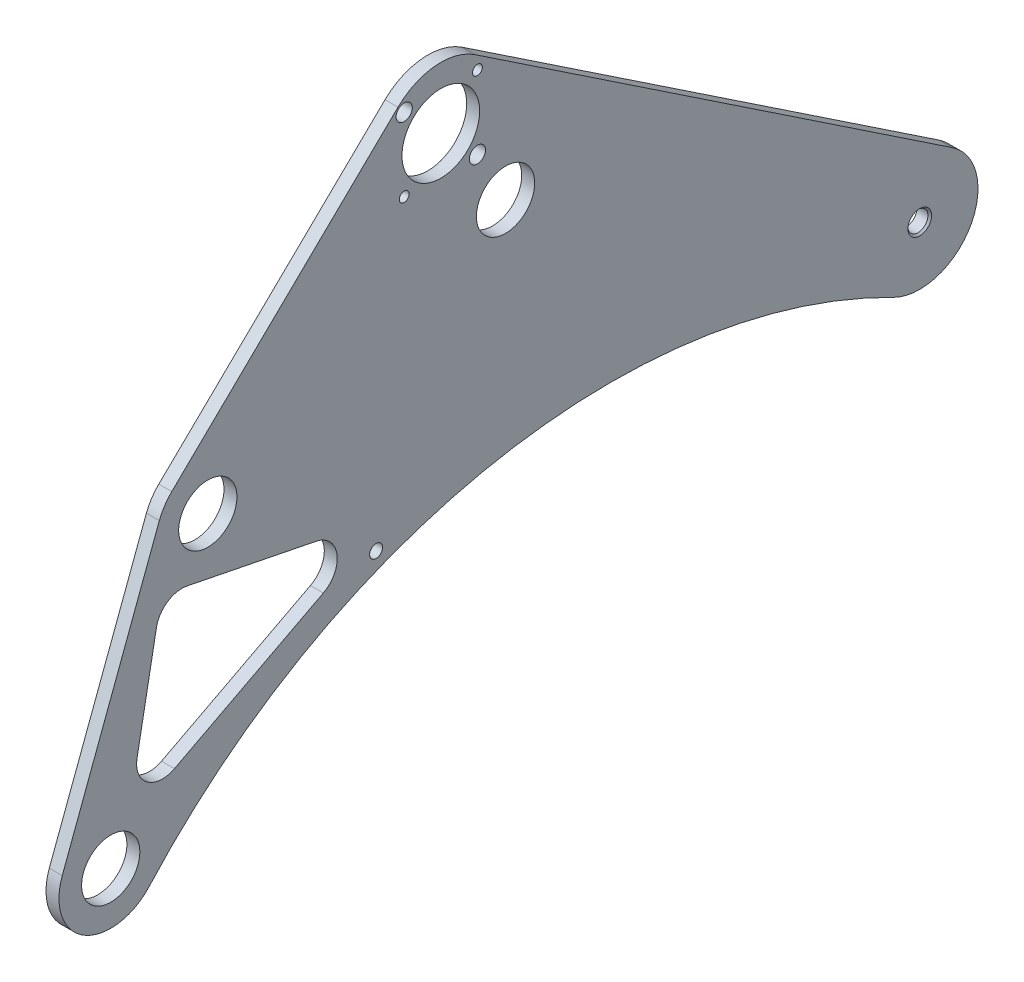
SolidWorks part; units mm, degrees
material "Acrylic (Medium-high impact)"
ref_plane "Front Plane" through (0, 0, 0) normal (0, 0, 1) x (1, 0, 0)
ref_plane "Top Plane" through (0, 0, 0) normal (0, 1, 0) x (1, 0, 0)
ref_plane "Right Plane" through (0, 0, 0) normal (1, 0, 0) x (0, 0, -1)
sketch "Sketch1" plane through (0, 0, 0) normal (1, 0, 0) x (0, 0, -1)
  line L0 (-548.7618, -304.8) -> (152.435, -304.8)
  line L1 (-192.8252, -101.6) -> (-152.4, -101.6)
  line L2 (-234.95, -143.7248) -> (-234.95, -186.4752)
  line L3 (-192.8252, -228.6) -> (-152.4, -228.6)
  line L4 (-152.4, -101.6) -> (-152.4, -228.6)
  circle A1 centre (0, 0) radius 6.35
  circle A6 centre (-396.875, -76.2) radius 9.525
  circle A7 centre (-349.25, 50.8) radius 9.525
  circle A8 centre (-203.2, 111.125) radius 9.525
  arc A9 (-234.95, -186.4752) -> (-192.8252, -228.6) centre (-192.8252, -186.4752) ccw
  arc A10 (-192.8252, -101.6) -> (-234.95, -143.7248) centre (-192.8252, -143.7248) ccw
  circle A11 centre (-355.7611, -180.5063) radius 120.65
  circle A12 centre (-234.95, 155.194) radius 29.845
  dimension "D1" = 12.7
  dimension "D2" = 19.05
  dimension "D3" = 42.1248
  dimension "D4" = 127
  dimension "D7" = 203.2
  dimension "D6" = 241.3
  dimension "D16" = 59.69
  dimension "D5" = 82.55
  dimension "D8" = 304.8
  dimension "D9" = 152.4
  dimension "D10" = 396.875
  dimension "D11" = 76.2
  dimension "D12" = 349.25
  dimension "D13" = 50.8
  dimension "D14" = 203.2
  dimension "D15" = 111.125
  dimension "D17" = 234.95
  dimension "D18" = 155.194
sketch "Sketch2" plane through (0, 0, 0) normal (1, 0, 0) x (0, 0, -1)
  line L1 (-420.6578, -67.2815) -> (-373.0328, 59.7185)
  line L3 (-366.9483, 69.0189) -> (-255.9667, 176.829)
  line L5 (-218.1841, 180.2675) -> (15.8835, 23.7539)
  line L6 (-1001.8623, -101.6) -> (216.545, -101.6) construction
  line L7 (-1029.8132, 185.3565) -> (188.5941, 185.3565) construction
  arc A0 (-366.9483, 69.0189) -> (-373.0328, 59.7185) centre (-349.25, 50.8) ccw
  arc A2 (-420.6578, -67.2815) -> (-377.9906, -93.1865) centre (-396.875, -76.2) ccw
  arc A4 (-218.1841, 180.2675) -> (-255.9667, 176.829) centre (-234.95, 155.194) ccw
  arc A5 (-12.9753, -25.4592) -> (15.8835, 23.7539) centre (0, 0) ccw
  arc A8 (-377.9906, -93.1865) -> (-12.9753, -25.4592) centre (-151.3783, -297.0244) cw
  circle A12 centre (-396.875, -76.2) radius 9.525 construction
  circle A13 centre (-349.25, 50.8) radius 9.525 construction
  dimension "D1" = 25.4
  dimension "D2" = 57.15
  dimension "D3" = 60.325
  dimension "D4" = 304.8
  dimension "D6" = 286.9565
extrude "Boss-Extrude1" add sketch "Sketch2" along normal blind 6.35
sketch "Sketch3" plane through (6.35, 0, 0) normal (1, 0, 0) x (0, 0, -1)
  line L0 (-216.9895, 173.1545) -> (-252.9105, 137.2335) construction
  line L1 (-234.95, 155.194) -> (-234.95, 205.0182) construction
  line L2 (-252.9105, 173.1545) -> (-216.9895, 137.2335) construction
  circle A0 centre (-203.2, 111.125) radius 14.2875
  circle A1 centre (-349.25, 50.8) radius 14.2875
  circle A2 centre (-396.875, -76.2) radius 14.2875
  circle A3 centre (-234.95, 155.194) radius 19.05
  circle A5 centre (-252.9105, 137.2335) radius 2.413
  circle A7 centre (-216.9895, 137.2335) radius 3.9687
  circle A8 centre (-216.9895, 173.1545) radius 2.413
  circle A9 centre (-252.9105, 173.1545) radius 3.9687
  point P18 (-234.95, 155.194)
  point P28 (-234.95, 155.194)
  dimension "D1" = 38.1
  dimension "D2" = 28.575
  dimension "D3" = 4.826
  dimension "D4" = 50.8
  dimension "D5" = 45
  dimension "D6" = 7.9375
  dimension "D7" = 50.8
extrude "Cut-Extrude1" cut sketch "Sketch3" against normal up to next
hole_wizard "3/8 Clearance Hole2" positions "Sketch7" profile "Sketch8" hole size "3/8" standard "ANSI Inch" end condition through all
sketch "Sketch7" plane through (6.35, 0, 0) normal (1, 0, 0) x (0, 0, -1)
  point P0 (0, 0)
sketch "Sketch8" plane through (6.35, 0, 0) normal (0, 1, 0) x (0, 0, -1)
  line L0 (0, 0) -> (0, 6.35)
  line L1 (0, 6.35) -> (4.9022, 6.35)
  line L2 (4.9022, 6.35) -> (4.9022, 0.8915)
  line L3 (4.9022, 0.8915) -> (5.7937, 0)
  line L5 (5.7937, 0) -> (0, 0)
  line L6 (-4.9022, 0.8915) -> (-5.7937, 0) construction
  line L11 (0, -6.35) -> (0, 107.95) construction
  dimension "Thru Hole Dia." = 9.8044
  dimension "Thru Hole Depth" = 6.35
  dimension "Near C'Sink Dia." = 11.5875
  dimension "Near C'Sink Angle" = 90
sketch "Sketch9" plane through (6.35, 0, 0) normal (1, 0, 0) x (0, 0, -1)
  line L0 (-495.9857, -101.6) -> (27.4607, -101.6) construction
  line L1 (100.4878, 185.3565) -> (-422.9585, 185.3565) construction
  arc A0 (-218.1841, 180.2675) -> (-255.9667, 176.829) centre (-234.95, 155.194) ccw construction
  arc A1 (-420.6578, -67.2815) -> (-377.9906, -93.1865) centre (-396.875, -76.2) ccw construction
  dimension "D1" = 286.9565
hole_wizard "1/4 (0.2500) Dowel Hole2" positions "Sketch12" profile "Sketch13" hole size "1/4" standard "ANSI Inch" end condition through all
sketch "Sketch12" plane through (6.35, 0, 0) normal (1, 0, 0) x (0, 0, -1)
  point P0 (-266.7, -6.35)
  dimension "D1" = 266.7
sketch "Sketch13" plane through (6.35, -6.35, 266.7) normal (0, 1, 0) x (0, 0, -1)
  line L0 (0, 0) -> (0, 6.35)
  line L1 (0, 6.35) -> (3.175, 6.35)
  line L2 (3.175, 6.35) -> (3.175, 0)
  line L5 (3.175, 0) -> (0, 0)
  line L11 (0, -6.35) -> (0, 107.95) construction
  dimension "Thru Hole Dia." = 6.35
  dimension "Thru Hole Depth" = 6.35
sketch "Sketch14" plane through (6.35, 0, 0) normal (1, 0, 0) x (0, 0, -1)
  line L0 (-365.6004, -49.3596) -> (-292.5754, -11.2596)
  line L1 (-295.9593, 12.4534) -> (-359.4593, 25.1534)
  line L2 (-374.4325, 15.0405) -> (-383.9575, -35.7595)
  arc A0 (-383.9575, -35.7595) -> (-365.6004, -49.3596) centre (-371.475, -38.1) ccw
  arc A1 (-292.5754, -11.2596) -> (-295.9593, 12.4534) centre (-298.45, 0) ccw
  arc A2 (-359.4593, 25.1534) -> (-374.4325, 15.0405) centre (-361.95, 12.7) ccw
  circle A3 centre (-396.875, -76.2) radius 14.2875 construction
  circle A4 centre (-349.25, 50.8) radius 14.2875 construction
  circle A5 centre (-266.7, -6.35) radius 3.175 construction
  point P21 (0, 0)
  dimension "D1" = 38.1
  dimension "D2" = 25.4
  dimension "D3" = 25.4
  dimension "D4" = 38.1
  dimension "D5" = 12.7
  dimension "D6" = 31.75
  dimension "D7" = 6.35
  dimension "D8" = 25.4
extrude "Cut-Extrude2" cut sketch "Sketch14" against normal through all
